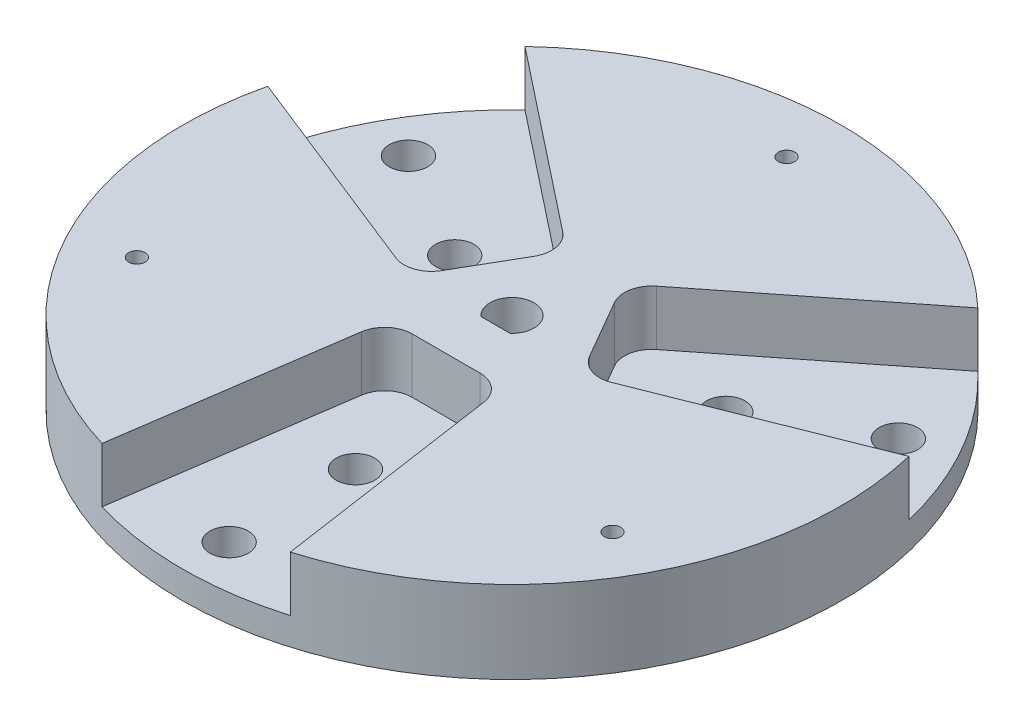
SolidWorks part; units mm, degrees
ref_plane "Front Plane" through (0, 0, 0) normal (0, 0, 1) x (1, 0, 0)
ref_plane "Top Plane" through (0, 0, 0) normal (0, 1, 0) x (1, 0, 0)
ref_plane "Right Plane" through (0, 0, 0) normal (1, 0, 0) x (0, 0, -1)
sketch "Sketch1" plane through (0, 0, 0) normal (0, 1, 0) x (1, 0, 0)
  circle A0 centre (0, 0) radius 60
  dimension "D1" = 120
extrude "Boss-Extrude1" add sketch "Sketch1" along normal blind 15
sketch "Sketch2" plane through (0, 15, 0) normal (0, 1, 0) x (1, 0, 0)
  line L0 (0, 60) -> (0, -60) construction
  line L1 (-60, 0) -> (60, 0) construction
  line L2 (-2.6458, -3) -> (2.6458, -3)
  line L3 (0, 4) -> (0, 0) construction
  line L4 (-17.5, -60) -> (17.5, -60)
  line L5 (17.5, -60) -> (10.5, -12)
  line L6 (10.5, -12) -> (-10.5, -12)
  line L7 (-10.5, -12) -> (-17.5, -60)
  circle A0 centre (0, 0) radius 60 construction
  arc A1 (2.6458, -3) -> (-2.6458, -3) centre (0, 0) ccw
  point P15 (0, -60)
  point P17 (0, -12)
  dimension "D1" = 8
  dimension "D2" = 3
  dimension "D3" = 21
  dimension "D4" = 35
  dimension "D5" = 48
extrude "Cut-Extrude1" cut sketch "Sketch2" against normal up to next contours L2 A1 region at (0, 15, -0.2647)
extrude "Cut-Extrude2" cut sketch "Sketch2<3>" against normal blind 10
sketch "Sketch2<3>" plane through (0, 15, 0) normal (0, 1, 0) x (1, 0, 0) same geometry as "Sketch2"
sketch "Sketch3" plane through (0, 5, 0) normal (0, 1, 0) x (1, 0, 0)
  line L0 (10.5, -12) -> (-10.5, -12) construction
  circle A0 centre (0, -28.5) radius 3.5
  circle A1 centre (0, -51.5) radius 3.5
  dimension "D1" = 7
  dimension "D2" = 7
  dimension "D3" = 16.5
  dimension "D4" = 23
extrude "Cut-Extrude3" cut sketch "Sketch3" against normal up to next
pattern_circular "CirPattern1" count 3 over 360 about axis through (0, -0.001, 0) along (0, 1, 0) of "Cut-Extrude2" reverse direction yes
pattern_circular "CirPattern2" count 3 over 360 about axis through (0, 15, 0) along (0, 1, 0) of "Cut-Extrude3"
fillet "Fillet1" radius 5 6 edges at (10.5, 10, 12) (-10.5, 10, 12) (-15.6423, 10, 3.0933) (-5.1423, 10, -15.0933) (15.6423, 10, 3.0933) (5.1423, 10, -15.0933)
sketch "Sketch4" plane through (0, 15, 0) normal (0, 1, 0) x (1, 0, 0)
  line L0 (-60, 0) -> (60, 0) construction
  line L1 (0, 60) -> (0, -60) construction
  line L2 (-51.9615, 30) -> (51.9615, -30) construction
  line L3 (51.9615, 30) -> (-51.9615, -30) construction
  arc A0 (-58.3652, 13.9107) -> (-17.1356, -57.5011) centre (0, 0) ccw construction
  arc A1 (17.1356, -57.5011) -> (58.3652, 13.9107) centre (0, 0) ccw construction
  arc A2 (41.2296, 43.5904) -> (-41.2296, 43.5904) centre (0, 0) ccw construction
  arc A3 (-17.1356, -57.5011) -> (17.1356, -57.5011) centre (0, 0) ccw construction
  circle A4 centre (0, 0) radius 50 construction
  circle A5 centre (0, 50) radius 1.5
  dimension "D1" = 100
  dimension "D4" = 3
  dimension "D2" = 30
  dimension "D3" = 30
extrude "Cut-Extrude4" cut sketch "Sketch4" against normal up to next
pattern_circular "CirPattern3" count 3 over 360 about axis through (0, -0.001, 0) along (0, 1, 0) of "Cut-Extrude4" reverse direction yes
sketch "Sketch5" plane through (0, 15, 0) normal (0, 1, 0) x (1, 0, 0)
  line L0 (-2.6458, -3) -> (2.6458, -3)
  arc A0 (-2.6458, -3) -> (2.6458, -3) centre (0, 0) ccw
  dimension "D1" = 4
extrude "Boss-Extrude2" add sketch "Sketch5" against normal up to body separate body
